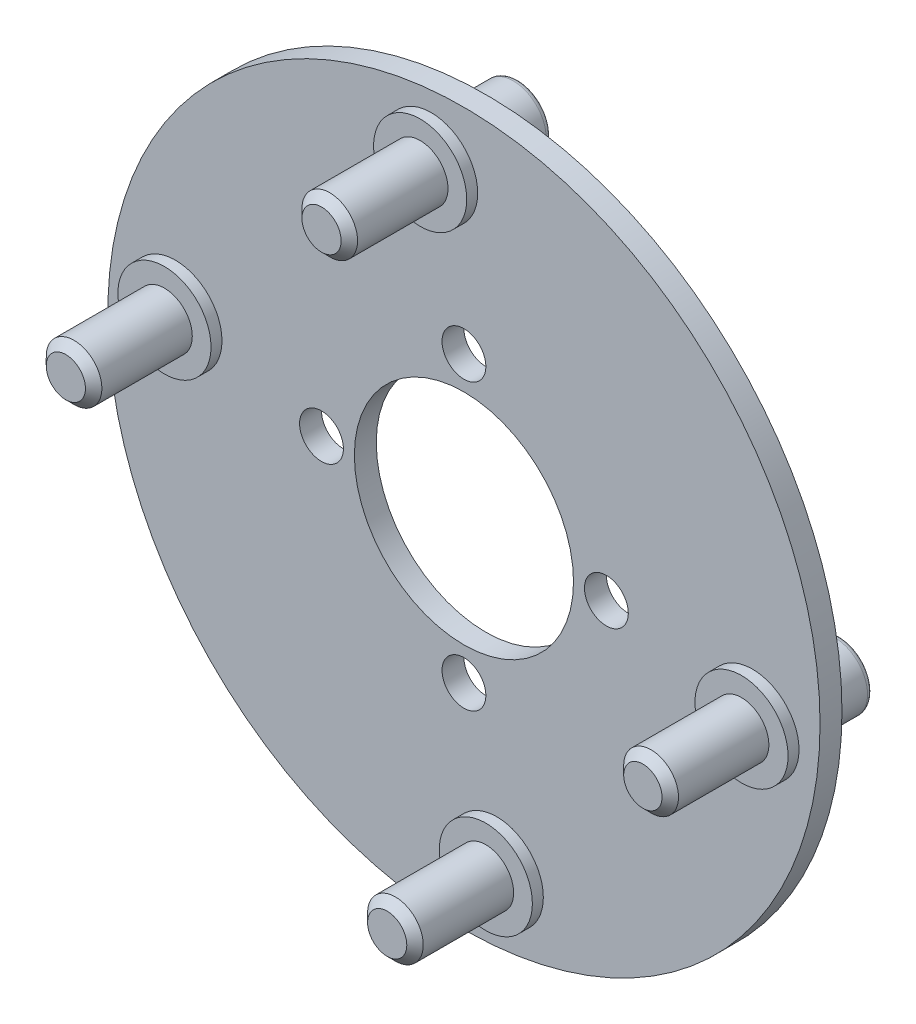
SolidWorks part; units mm, degrees
ref_plane "Plan de face" through (0, 0, 0) normal (0, 0, 1) x (1, 0, 0)
ref_plane "Plan de dessus" through (0, 0, 0) normal (0, 1, 0) x (1, 0, 0)
ref_plane "Plan de droite" through (0, 0, 0) normal (1, 0, 0) x (0, 0, -1)
sketch "Esquisse1" plane through (0, 0, 0) normal (0, 0, 1) x (1, 0, 0)
  circle A0 centre (0, 0) radius 32.5
  circle A1 centre (0, 0) radius 10
  dimension "D1" = 65
  dimension "D2" = 20
extrude "Extrusion1" add sketch "Esquisse1" along normal blind 2
sketch "Esquisse2" plane through (0, 0, 0) normal (0, 0, -1) x (-1, 0, 0)
  line L0 (0, 0) -> (0, 23.5916) construction
  circle A0 centre (0, 13) radius 2
  dimension "D1" = 4
  dimension "D2" = 13
extrude "Enlèv. mat.-Extru.1" cut sketch "Esquisse2" against normal through all
ref_axis "Axe1" through (0, 0, 2) along (0, 0, -1)
pattern_circular "Répétition circulaire1" count 4 over 360 about axis through (0, 0, 2) along (0, 0, -1) of "Enlèv. mat.-Extru.1"
sketch "Esquisse3" plane through (0, 0, 2) normal (0, 0, 1) x (1, 0, 0)
  line L0 (0, 0) -> (0, 21.8774) construction
  line L1 (0, 0) -> (-16.4095, 16.4095) construction
  line L2 (-5.0904, 28.4249) -> (27.3423, -4.0078) construction
  line L3 (-27.4777, 4.1431) -> (4.2334, -27.5679) construction
  circle A0 centre (0, 0) radius 26.5 construction
  circle A1 centre (-2.9956, 26.3301) radius 4.25
  circle A2 centre (-26.3301, 2.9956) radius 4.25
  circle A3 centre (2.9956, -26.3301) radius 4.25
  circle A4 centre (26.3301, -2.9956) radius 4.25
  dimension "D2" = 53
  dimension "D5" = 8.5
  dimension "D1" = 45
  dimension "D3" = 33
  dimension "D4" = 16.5
extrude "Extrusion2" add sketch "Esquisse3" along normal blind 1 and the other way blind 3.5
sketch "Esquisse4" plane through (0, 0, -1.5) normal (0, 0, -1) x (-1, 0, 0)
  circle A0 centre (2.9956, 26.3301) radius 3
  circle A1 centre (-26.3301, -2.9956) radius 3
  circle A2 centre (-2.9956, -26.3301) radius 3
  circle A3 centre (26.3301, 2.9956) radius 3
  dimension "D1" = 6
extrude "Extrusion3" add sketch "Esquisse4" along normal blind 4.5
fillet "Congé1" radius 0.5 8 edges at (-29.3301, 2.9956, -6) (-0.0044, -26.3301, -6) (23.3301, -2.9956, -6) (-5.9956, 26.3301, -6) (7.2456, -26.3301, -1.5) (-22.0801, 2.9956, -1.5) (1.2544, 26.3301, -1.5) (30.5801, -2.9956, -1.5)
sketch "Esquisse5" plane through (0, 0, 3) normal (0, 0, 1) x (1, 0, 0)
  circle A0 centre (-2.9956, 26.3301) radius 2.5395
  circle A1 centre (26.3301, -2.9956) radius 2.5
  circle A2 centre (-26.3301, 2.9956) radius 2.5395
  circle A3 centre (2.9956, -26.3301) radius 2.5395
  dimension "D1" = 5
extrude "Extrusion4" add sketch "Esquisse5" along normal blind 9
cosmetic thread "Représentation de filetage1" parameters "D1"=9, "D2"=3.25
cosmetic thread "Représentation de filetage2" parameters "D1"=9, "D2"=3.25
cosmetic thread "Représentation de filetage3" parameters "D1"=9, "D2"=3.25
cosmetic thread "Représentation de filetage4" parameters "D1"=9, "D2"=3.25
chamfer "Chanfrein1" distance 0.75 angle 45 4 edges at (-23.7907, 2.9956, 12) (5.5351, -26.3301, 12) (28.8301, -2.9956, 12) (-0.4562, 26.3301, 12)
